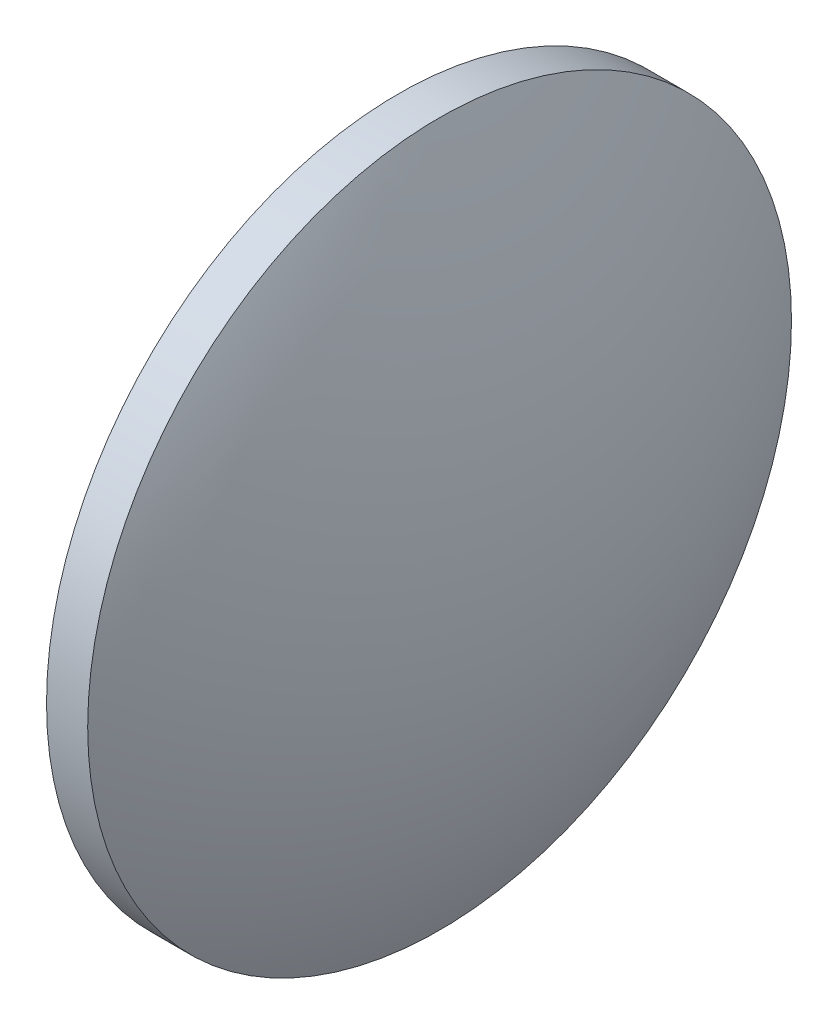
SolidWorks part; units mm, degrees
material "Ceramic Porcelain"
ref_plane "Front Plane" through (0, 0, 0) normal (0, 0, 1) x (1, 0, 0)
ref_plane "Top Plane" through (0, 0, 0) normal (0, 1, 0) x (1, 0, 0)
ref_plane "Right Plane" through (0, 0, 0) normal (1, 0, 0) x (0, 0, -1)
sketch "Sketch1" plane through (0, 0, 0) normal (1, 0, 0) x (0, 0, -1)
  circle A0 centre (0, 0) radius 21.37
  dimension "D1" = 42.74
extrude "Boss-Extrude1" add sketch "Sketch1" along normal blind 2.5
dome "Dome1" faces to dome 1 distance 5 reverse direction no elliptical dome no face at (2.5, 0, -21.37) parameters "D1"=5
